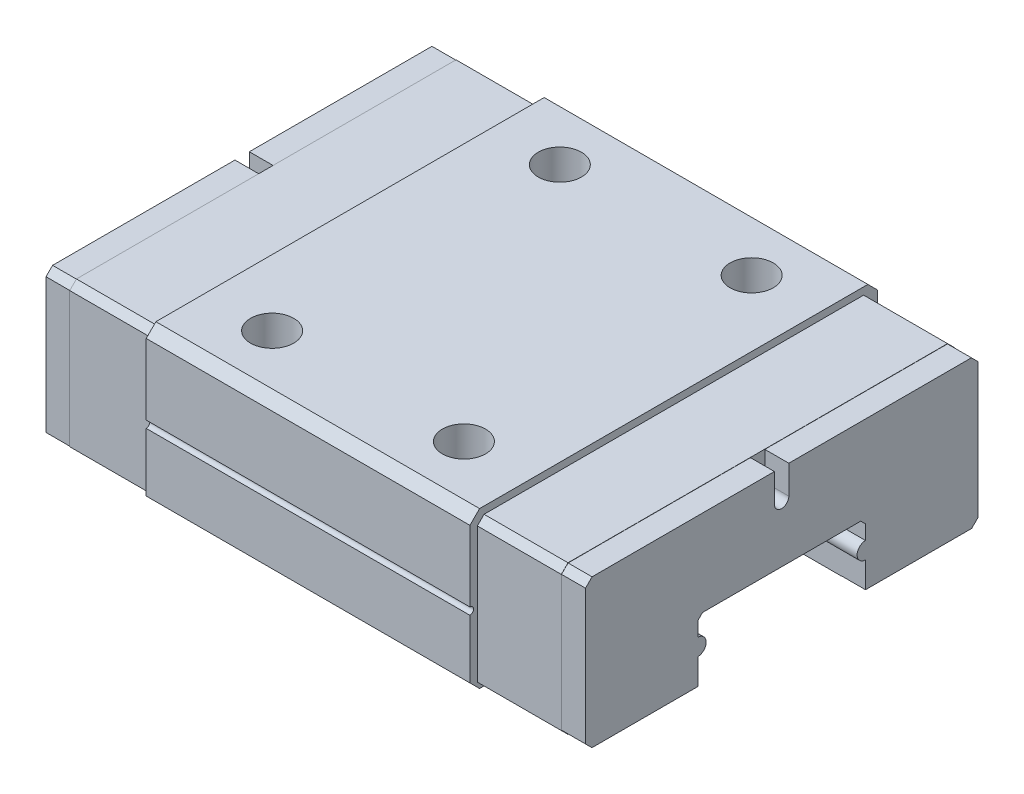
SolidWorks part; units mm, degrees
ref_plane "前视基准面" through (0, 0, 0) normal (0, 0, 1) x (1, 0, 0)
ref_plane "上视基准面" through (0, 0, 0) normal (0, 1, 0) x (1, 0, 0)
ref_plane "右视基准面" through (0, 0, 0) normal (1, 0, 0) x (0, 0, -1)
sketch "草图1" plane through (0, 0, 0) normal (1, 0, 0) x (0, 0, -1)
  line L0 (0, 0) -> (0, 6.9969) construction
  line L1 (0, 0) -> (6.5228, 0) construction
  line L2 (-8.5, 2.8469) -> (-8.0969, 3.25)
  line L3 (-8.0969, 3.25) -> (8.0969, 3.25)
  line L4 (-8.5, 2.8469) -> (-8.5, -2.8469)
  line L5 (-8.0969, -3.25) -> (8.0969, -3.25)
  line L6 (8.5, 2.8469) -> (8.5, -2.8469)
  line L7 (-8.5, 3.25) -> (8.5, -3.25) construction
  line L8 (-8.5, -3.25) -> (8.5, 3.25) construction
  line L9 (8.0969, 3.25) -> (8.5, 2.8469)
  line L10 (8.0969, -3.25) -> (8.5, -2.8469)
  line L11 (-8.5, -2.8469) -> (-8.0969, -3.25)
  point P1 (0, 0)
  dimension "D1" = 6.5
  dimension "D2" = 17
  dimension "D3" = 0.57
  dimension "D5" = 0.57
  dimension "D9" = 0.57
  dimension "D10" = 225
  dimension "D7" = 0.57
  dimension "D4" = 225
  dimension "D6" = 225
  dimension "D8" = 225
extrude "凸台-拉伸1" add sketch "草图1" along normal blind 13.5
sketch "草图3" plane through (0, 0, 0) normal (-1, 0, 0) x (0, 0, 1)
  line L0 (0, 0) -> (0, 6.7455) construction
  line L1 (0, 0) -> (9.8711, 0) construction
  line L3 (8.5, 2.8469) -> (8.5, -2.8469) construction
  circle A0 centre (8.5, -0.2531) radius 0.15
  circle A1 centre (-8.5, -0.2531) radius 0.15
  point P8 (0, 0)
  point P10 (0, 0)
  dimension "D1" = 0.3
  dimension "D2" = 3.1
extrude "切除-拉伸2" cut sketch "草图3" against normal up to surface (13.5 mm away) up to face at (13.5, 0, 0)
sketch "草图4" plane through (0, 0, 0) normal (-1, 0, 0) x (0, 0, 1)
  line L0 (0, 0) -> (0, 6.8579) construction
  line L1 (0, 0) -> (4.1985, 0) construction
  line L3 (8.19, -2.9702) -> (8.19, 2.67)
  line L4 (-8.2, -2.9702) -> (-8.2, 2.67)
  line L5 (7.91, 2.95) -> (-7.92, 2.95)
  line L6 (8.0969, -3.25) -> (-8.0969, -3.25) construction
  line L7 (-8.2, 2.95) -> (8.2, -3.25) construction
  line L8 (8.19, 2.95) -> (-8.21, -3.25) construction
  line L9 (-8.0969, 3.25) -> (8.0969, 3.25) construction
  line L10 (-8.5, -2.8469) -> (-8.5, -0.4031) construction
  line L11 (-8.2, 2.67) -> (-7.92, 2.95)
  line L12 (-7.9302, -3.24) -> (-8.2, -2.9702)
  line L13 (7.9202, -3.24) -> (8.19, -2.9702)
  line L14 (8.19, 2.67) -> (7.91, 2.95)
  line L15 (-7.9302, -3.24) -> (7.9202, -3.24)
  point P12 (0, -0.15)
  dimension "D1" = 0.3
  dimension "D2" = 0.3
  dimension "D3" = 0.01
  dimension "D4" = 225
  dimension "D5" = 225
extrude "凸台-拉伸2" add sketch "草图4" along normal blind 3.5 and the other way blind 17
sketch "草图5" plane through (17, 0, 0) normal (1, 0, 0) x (0, 0, -1)
  line L9 (-7.9059, 2.94) -> (7.9159, 2.94)
  line L10 (7.9159, 2.94) -> (8.19, 2.6659)
  line L11 (8.19, 2.6659) -> (8.19, -2.966)
  line L12 (8.19, -2.966) -> (7.926, -3.23)
  line L13 (7.926, -3.23) -> (-7.9102, -3.23)
  line L14 (-7.9102, -3.23) -> (-8.18, -2.9602)
  line L15 (-8.18, -2.9602) -> (-8.18, 2.6659)
  line L16 (-8.18, 2.6659) -> (-7.9059, 2.94)
  line L17 (-8.19, 2.67) -> (-7.91, 2.95) construction
  line L18 (-7.9202, -3.24) -> (-8.19, -2.9702) construction
  line L20 (7.92, 2.95) -> (8.2, 2.67) construction
  line L21 (8.2, -2.9702) -> (7.9302, -3.24) construction
  line L22 (-7.91, 2.95) -> (7.92, 2.95) construction
  line L23 (7.9302, -3.24) -> (-7.9202, -3.24) construction
  line L24 (8.2, 2.67) -> (8.2, -2.9702) construction
  line L25 (-8.19, -2.9702) -> (-8.19, 2.67) construction
  point P2 (0.1949, 6.7788)
  point P17 (4.3339, -0.5333)
  point P26 (8.2, -1.6177)
  point P27 (8.2, 2.0305)
  point P28 (-8.19, 2.3747)
  point P29 (-8.18, -3.014)
  point P30 (-8.18, -2.9448)
  dimension "D1" = 0.01
  dimension "D2" = 0.01
  dimension "D3" = 0.01
  dimension "D4" = 0.01
  dimension "D5" = 0.01
  dimension "D6" = 0.01
  dimension "D7" = 0.01
extrude "凸台-拉伸3" add sketch "草图5" along normal blind 1 and the other way blind 21.5
sketch "草图2" plane through (0, 3.25, 0) normal (0, 1, 0) x (1, 0, 0)
  line L0 (6.75, 0) -> (0, 0) construction
  line L1 (2.75, 6) -> (10.75, 6) construction
  line L2 (2.75, 6) -> (2.75, -6) construction
  line L3 (2.75, -6) -> (10.75, -6) construction
  line L4 (10.75, 6) -> (10.75, -6) construction
  line L5 (2.75, 6) -> (10.75, -6) construction
  line L6 (2.75, -6) -> (10.75, 6) construction
  line L8 (0, 8.0969) -> (0, -8.0969) construction
  circle A0 centre (2.75, 6) radius 0.9
  circle A1 centre (10.75, 6) radius 0.9
  circle A2 centre (10.75, -6) radius 0.9
  circle A3 centre (2.75, -6) radius 0.9
  point P0 (6.75, 0)
  dimension "D1" = 1.8
  dimension "D2" = 12
  dimension "D3" = 8
  dimension "D4" = 2.75
extrude "切除-拉伸1" cut sketch "草图2" against normal blind 2.5
sketch "草图6" plane through (18, 0, 0) normal (1, 0, 0) x (0, 0, -1)
  line L0 (0, 0) -> (0, 6.1749) construction
  line L1 (7.9159, 2.94) -> (-7.9059, 2.94) construction
  line L2 (0.3, 1.75) -> (0.3, 2.94)
  line L3 (-0.3, 1.75) -> (-0.3, 2.94)
  line L4 (-0.3, 2.94) -> (0.3, 2.94)
  circle A0 centre (0, 1.75) radius 0.3 construction
  arc A1 (-0.3, 1.75) -> (0.3, 1.75) centre (0, 1.75) ccw
  dimension "D1" = 0.6
  dimension "D2" = 1.19
extrude "切除-拉伸3" cut sketch "草图6" against normal blind 1
sketch "草图7" plane through (-4.5, 0, 0) normal (-1, 0, 0) x (0, 0, 1)
  line L0 (0, 0) -> (0, 4.4194) construction
  line L1 (-0.3, 1.75) -> (-0.3, 2.94)
  line L3 (0.3, 1.75) -> (0.3, 2.94)
  line L4 (-7.9159, 2.94) -> (7.9059, 2.94) construction
  line L5 (0.3, 2.94) -> (-0.3, 2.94)
  circle A0 centre (0, 1.75) radius 0.3 construction
  arc A1 (-0.3, 1.75) -> (0.3, 1.75) centre (0, 1.75) ccw
  dimension "D1" = 0.6
  dimension "D2" = 1.19
extrude "切除-拉伸4" cut sketch "草图7" against normal blind 1
sketch "草图8" plane through (-4.5, 0, 0) normal (-1, 0, 0) x (0, 0, 1)
  circle A0 centre (0, 1.75) radius 0.3
  arc A1 (-0.3, 1.75) -> (0.3, 1.75) centre (0, 1.75) ccw construction
extrude "切除-拉伸5" cut sketch "草图8" against normal up to surface (4.5 mm away) up to face at (0, -0.1475, -0.005)
sketch "草图9" plane through (18, 0, 0) normal (1, 0, 0) x (0, 0, -1)
  circle A0 centre (0, 1.75) radius 0.3
  arc A1 (-0.3, 1.75) -> (0.3, 1.75) centre (0, 1.75) ccw construction
extrude "切除-拉伸6" cut sketch "草图9" against normal up to surface (4.5 mm away) contours A0 up to face at (13.5, -0.1475, -0.005)
sketch "草图10" plane through (18, 0, 0) normal (1, 0, 0) x (0, 0, -1)
  line L0 (3.498, -2.15) -> (3.498, -3.25)
  line L1 (-8.0969, -3.25) -> (8.0969, -3.25) construction
  line L2 (0, -0.7312) -> (0, 0.7312) construction
  line L3 (0, 0) -> (2.7709, 0) construction
  line L4 (3.498, -1.45) -> (3.498, -0.85)
  line L5 (3.498, -0.85) -> (3.3, -0.652)
  line L6 (3.3, -0.652) -> (-3.3, -0.652)
  line L7 (-3.498, -2.15) -> (-3.498, -3.25)
  line L8 (-3.498, -1.45) -> (-3.498, -0.85)
  line L9 (-3.498, -0.85) -> (-3.3, -0.652)
  line L10 (-3.498, -3.25) -> (3.498, -3.25)
  circle A0 centre (3.498, -1.8) radius 0.35 construction
  arc A1 (3.498, -2.15) -> (3.498, -1.45) centre (3.498, -1.8) cw
  arc A2 (-3.498, -2.15) -> (-3.498, -1.45) centre (-3.498, -1.8) ccw
  point P8 (0, 0)
  point P25 (0, -0.652)
  dimension "D2" = 0.7
  dimension "D1" = 1.1
  dimension "D3" = 0.6
  dimension "D4" = 225
  dimension "D5" = 0.28
  dimension "D6" = 3.3
extrude "切除-拉伸7" cut sketch "草图10" against normal up to surface (22.5 mm away) up to face at (-4.5, 0.6588, -0.0038)
